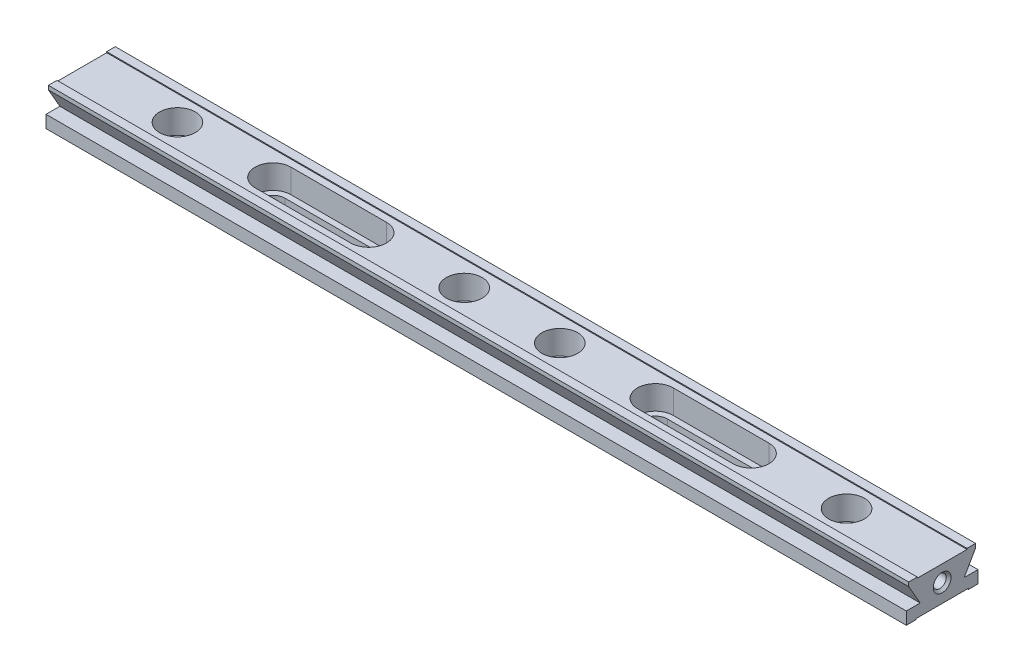
SolidWorks part; units mm, degrees
ref_plane "Front Plane" through (0, 0, 0) normal (0, 0, 1) x (1, 0, 0)
ref_plane "Top Plane" through (0, 0, 0) normal (0, 1, 0) x (1, 0, 0)
ref_plane "Right Plane" through (0, 0, 0) normal (1, 0, 0) x (0, 0, -1)
sketch "Sketch1" plane through (0, 0, 0) normal (1, 0, 0) x (0, 0, -1)
  line L0 (0, -1.0235) -> (0, 0.5734) construction
  line L2 (9.525, -0.254) -> (9.525, 3.048)
  line L3 (9.525, 3.048) -> (5.842, 3.048)
  line L4 (5.842, 3.048) -> (8.89, 8.3273)
  line L5 (8.89, 8.3273) -> (8.89, 9.398)
  line L6 (8.89, 9.398) -> (6.604, 9.398)
  line L7 (6.604, 9.398) -> (6.604, 9.144)
  line L8 (6.604, 9.144) -> (0, 9.144)
  line L9 (0, 9.144) -> (0, 0)
  line L10 (9.525, -0.254) -> (6.985, -0.254)
  line L11 (6.985, -0.254) -> (6.985, 0)
  line L12 (6.985, 0) -> (0, 0)
  point P12 (0, 4.826)
  dimension "D2" = 4.572
  dimension "D3" = 9.525
  dimension "D1" = 0.254
  dimension "D4" = 9.652
  dimension "D5" = 6.35
  dimension "D6" = 8.89
  dimension "D7" = 0.254
  dimension "D8" = 2.286
  dimension "D9" = 2.54
  dimension "D10" = 60
  dimension "D11" = 1.143
extrude "Boss-Extrude1" add sketch "Sketch1" along normal blind 228.6 contours L8 L9 L12 L11 L10 L2 L3 L4 L5 L6 L7
mirror "Mirror1" about plane through (0, 0, 0) normal (0, 0, 1) of "Boss-Extrude1"
hole_wizard "Tap Drill for #8-32 Tap2" positions "Sketch3" profile "Sketch4" hole size "#8-32" standard "ANSI Inch"
sketch "Sketch3" plane through (0, 0, 0) normal (-1, 0, 0) x (0, 0, 1)
  point P0 (0, 4.826)
sketch "Sketch4" plane through (0, 4.826, 0) normal (0, 1, 0) x (0, 0, 1)
  line L0 (0, 0) -> (0, 13.7378)
  line L1 (0, 13.7378) -> (1.7272, 12.7)
  line L2 (1.7272, 12.7) -> (1.7272, 0.635)
  line L3 (1.7272, 0.635) -> (2.3622, 0)
  line L5 (2.3622, 0) -> (0, 0)
  line L6 (-1.7272, 0.635) -> (-2.3622, 0) construction
  line L10 (0, 13.7378) -> (-1.7272, 12.7) construction
  line L11 (0, -6.35) -> (0, 107.95) construction
  dimension "Hole Dia." = 3.4544
  dimension "Hole Depth" = 12.7
  dimension "Near C'Sink Dia." = 4.7244
  dimension "Near C'Sink Angle" = 90
  dimension "Drill Angle" = 118
ref_plane "Plane1" through (114.3, 0, 0) normal (-1, 0, 0) x (0, 0, 1)
mirror "Mirror2" about plane through (114.3, 0, 0) normal (-1, 0, 0) of "Tap Drill for #8-32 Tap2"
sketch "Sketch5" plane through (0, 9.144, 0) normal (0, 1, 0) x (1, 0, 0)
  line L0 (50.8, 0) -> (76.2, 0) construction
  line L1 (50.8, 3.175) -> (76.2, 3.175)
  line L2 (50.8, -3.175) -> (76.2, -3.175)
  line L3 (0, 6.604) -> (0, -6.604) construction
  line L4 (152.4, 0) -> (177.8, 0) construction
  line L5 (152.4, 3.175) -> (177.8, 3.175)
  line L6 (152.4, -3.175) -> (177.8, -3.175)
  line L7 (228.6, 6.604) -> (228.6, -6.604) construction
  line L8 (50.8, 4.7625) -> (76.2, 4.7625)
  line L9 (50.8, -4.7625) -> (76.2, -4.7625)
  line L10 (152.4, 4.7625) -> (177.8, 4.7625)
  line L11 (152.4, -4.7625) -> (177.8, -4.7625)
  circle A0 centre (25.4, 0) radius 3.175
  circle A1 centre (101.6, 0) radius 3.175
  arc A2 (50.8, 3.175) -> (50.8, -3.175) centre (50.8, 0) ccw
  arc A3 (76.2, -3.175) -> (76.2, 3.175) centre (76.2, 0) ccw
  circle A4 centre (127, 0) radius 3.175
  arc A5 (152.4, 3.175) -> (152.4, -3.175) centre (152.4, 0) ccw
  arc A6 (177.8, -3.175) -> (177.8, 3.175) centre (177.8, 0) ccw
  circle A7 centre (203.2, 0) radius 3.175
  circle A8 centre (25.4, 0) radius 4.7625
  arc A9 (76.2, -4.7625) -> (76.2, 4.7625) centre (76.2, 0) ccw
  arc A10 (50.8, 4.7625) -> (50.8, -4.7625) centre (50.8, 0) ccw
  circle A11 centre (101.6, 0) radius 4.7625
  circle A12 centre (127, 0) radius 4.7625
  arc A13 (177.8, -4.7625) -> (177.8, 4.7625) centre (177.8, 0) ccw
  arc A14 (152.4, 4.7625) -> (152.4, -4.7625) centre (152.4, 0) ccw
  circle A15 centre (203.2, 0) radius 4.7625
  point P7 (63.5, 0)
  point P26 (165.1, 0)
  dimension "D1" = 3.175
  dimension "D10" = 9.525
  dimension "D2" = 25.4
  dimension "D3" = 50.8
  dimension "D4" = 101.6
  dimension "D5" = 25.4
  dimension "D6" = 25.4
  dimension "D7" = 25.4
  dimension "D8" = 50.8
  dimension "D11" = 25.4
  dimension "D9" = 1.5875
extrude "Cut-Extrude1" cut sketch "Sketch5" against normal through all contours A0 | L1 A3 L2 A2 | A1 | A4 | L5 A6 L6 A5 | A7
extrude "Cut-Extrude2" cut sketch "Sketch5<4>" against normal blind 6.35 contours A8 | L8 A9 L9 A10 | A11 | A12 | L10 A13 L11 A14 | A15
sketch "Sketch5<4>" plane through (0, 9.144, 0) normal (0, 1, 0) x (1, 0, 0) same geometry as "Sketch5"
